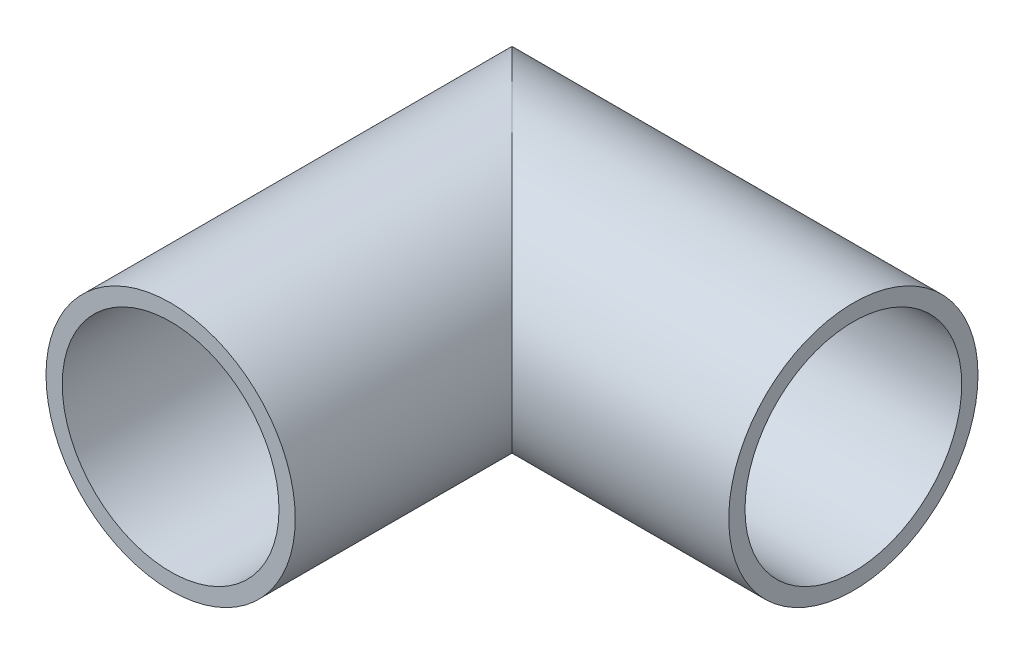
SolidWorks part; units mm, degrees
ref_plane "Front Plane" through (0, 0, 0) normal (0, 0, 1) x (1, 0, 0)
ref_plane "Top Plane" through (0, 0, 0) normal (0, 1, 0) x (1, 0, 0)
ref_plane "Right Plane" through (0, 0, 0) normal (1, 0, 0) x (0, 0, -1)
sketch "Sketch3" plane through (0, 0, 0) normal (0, 0, 1) x (1, 0, 0)
  circle A0 centre (0, 0) radius 14.605
  dimension "D1" = 29.21
extrude "Boss-Extrude2" add sketch "Sketch3" along normal blind 40.005
sketch "Sketch4" plane through (0, 0, 0) normal (1, 0, 0) x (0, 0, -1)
  circle A0 centre (0, 0) radius 14.605
extrude "Boss-Extrude3" add sketch "Sketch4" along normal blind 40.005
sketch "Sketch5" plane through (0, 0, 0) normal (-1, 0, 0) x (0, 0, 1)
  circle A0 centre (0, 0) radius 14.605
extrude "Boss-Extrude4" add sketch "Sketch5" along normal up to surface (14.605 mm away) up to face at (14.605, 0, 40.005)
sketch "Sketch6" plane through (0, 0, 40.005) normal (0, 0, 1) x (1, 0, 0)
  circle A0 centre (0, 0) radius 12.7
  dimension "D1" = 25.4
extrude "Cut-Extrude1" cut sketch "Sketch6" against normal blind 40.005
sketch "Sketch7" plane through (40.005, 0, 0) normal (1, 0, 0) x (0, 0, -1)
  circle A0 centre (0, 0) radius 12.7
  dimension "D1" = 25.4
extrude "Cut-Extrude2" cut sketch "Sketch7" against normal blind 40.005
sketch "Sketch8" plane through (0, 0, 0) normal (1, 0, 0) x (0, 0, -1)
  circle A0 centre (0, 0) radius 12.7
extrude "Cut-Extrude3" cut sketch "Sketch8" against normal up to surface (12.7 mm away) up to face at (0, 0, 6.35)
